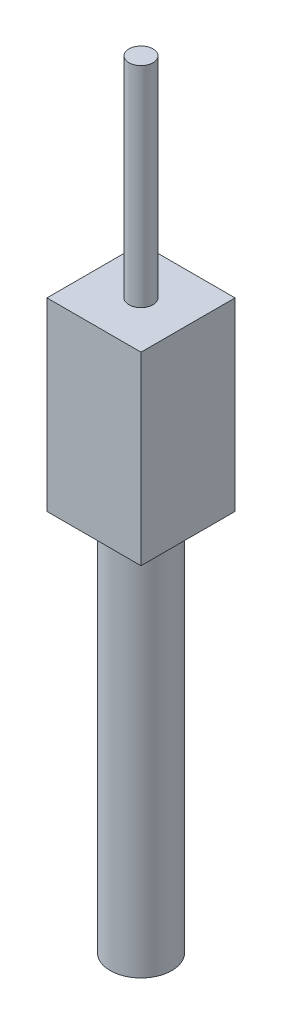
SolidWorks part; units mm, degrees
ref_plane "Front Plane" through (0, 0, 0) normal (0, 0, 1) x (1, 0, 0)
ref_plane "Top Plane" through (0, 0, 0) normal (0, 1, 0) x (1, 0, 0)
ref_plane "Right Plane" through (0, 0, 0) normal (1, 0, 0) x (0, 0, -1)
sketch "Sketch1" plane through (0, 0, 0) normal (0, 1, 0) x (1, 0, 0)
  circle A0 centre (0, 0) radius 5
  dimension "D1" = 10
extrude "Boss-Extrude1" add sketch "Sketch1" along normal blind 62
sketch "Sketch3" plane through (0, 62, 0) normal (0, 1, 0) x (1, 0, 0)
  line L1 (-7.625, -7.625) -> (7.625, -7.625)
  line L2 (-7.625, -7.625) -> (-7.625, 7.625)
  line L3 (-7.625, 7.625) -> (7.625, 7.625)
  line L4 (7.625, -7.625) -> (7.625, 7.625)
  line L5 (-7.625, -7.625) -> (7.625, 7.625) construction
  line L6 (-7.625, 7.625) -> (7.625, -7.625) construction
  point P0 (0, 0)
  dimension "D1" = 15.25
  dimension "D2" = 15.25
extrude "Boss-Extrude2" add sketch "Sketch3" along normal blind 30
sketch "Sketch4" plane through (0, 92, 0) normal (0, 1, 0) x (1, 0, 0)
  circle A0 centre (0, 0) radius 1.95
  dimension "D1" = 3.9
extrude "Boss-Extrude3" add sketch "Sketch4" along normal blind 34
sketch "Sketch5" plane through (0, 0, 0) normal (0, -1, 0) x (1, 0, 0)
  circle A0 centre (0, 0) radius 3
  dimension "D1" = 6
extrude "Cut-Extrude1" cut sketch "Sketch5" against normal blind 10
